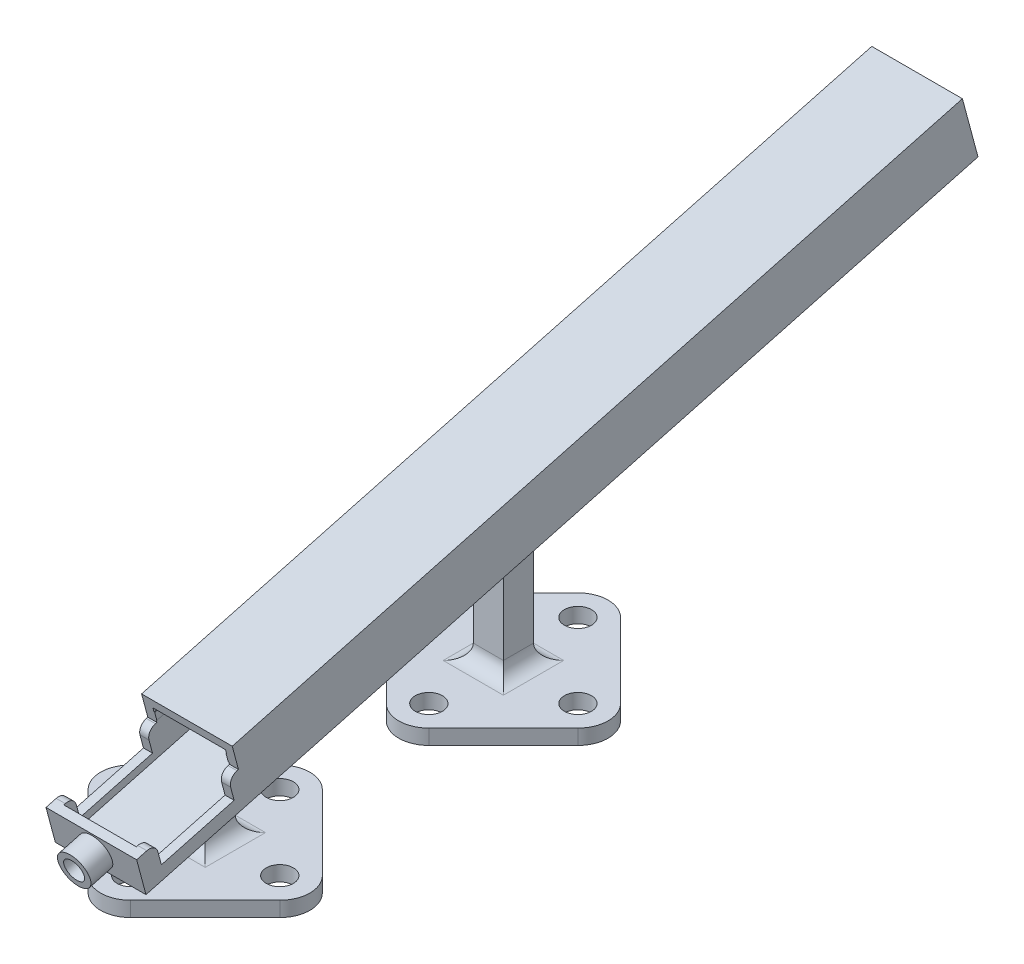
SolidWorks part; units mm, degrees
ref_plane "Front" through (0, 0, 0) normal (0, 0, 1) x (1, 0, 0)
ref_plane "Top" through (0, 0, 0) normal (0, 1, 0) x (1, 0, 0)
ref_plane "Right" through (0, 0, 0) normal (1, 0, 0) x (0, 0, -1)
ref_axis "Axis1" through (0, 55, 0) along (0, -1, 0)
ref_axis "Axis2" through (88.99, 0, 0) along (-1, 0, 0)
ref_axis "Axis3" through (0, 0, 55) along (0, 0, -1)
sketch "Sketch1" plane through (0, 0, 0) normal (0, 1, 0) x (1, 0, 0)
  line L0 (-24.75, 0) -> (0, 24.75) construction
  line L9 (-24.75, 0) -> (0, -24.75) construction
  line L11 (0, 24.75) -> (24.75, 0) construction
  line L12 (0, -24.75) -> (24.75, 0) construction
  line L13 (-24.75, 0) -> (24.75, 0) construction
  line L14 (0, 24.75) -> (0, -24.75) construction
  line L15 (-31.8211, 7.0711) -> (-7.0711, 31.8211)
  line L16 (7.0711, 31.8211) -> (31.8211, 7.0711)
  line L17 (7.0711, -31.8211) -> (31.8211, -7.0711)
  line L18 (-31.8211, -7.0711) -> (-7.0711, -31.8211)
  line L19 (0, -38.8921) -> (38.8921, 0) construction
  line L20 (-38.8921, 0) -> (0, -38.8921) construction
  line L21 (0, 38.8921) -> (38.8921, 0) construction
  line L22 (-38.8921, 0) -> (0, 38.8921) construction
  arc A4 (7.0711, -31.8211) -> (-7.0711, -31.8211) centre (0, -24.75) cw
  arc A5 (31.8211, 7.0711) -> (31.8211, -7.0711) centre (24.75, 0) cw
  arc A6 (-7.0711, 31.8211) -> (7.0711, 31.8211) centre (0, 24.75) cw
  arc A7 (-31.8211, 7.0711) -> (-31.8211, -7.0711) centre (-24.75, 0) ccw
  circle A8 centre (0, 24.75) radius 4.5
  circle A9 centre (24.75, 0) radius 4.5
  circle A10 centre (0, -24.75) radius 4.5
  circle A11 centre (-24.75, 0) radius 4.5
  point P1 (0, 0)
  dimension "D3" = 10
  dimension "D4" = 9
  dimension "D1" = 49.5
  dimension "D2" = 10
extrude "Boss-Extrude1" add sketch "Sketch1" along normal mid plane 5
ref_plane "Plane1" through (0, 0, 49.5) normal (0, 0, 1) x (1, 0, 0)
mirror "Mirror3" about plane through (0, 0, 49.5) normal (0, 0, 1) of bodies 101
sketch "Sketch2" plane through (0, 0, 0) normal (1, 0, 0) x (0, 0, -1)
  line L0 (-106.0711, 2.5) -> (-130.8211, 2.5) construction
  line L1 (-104, 2.5) -> (-94, 2.5)
  line L2 (-104, 2.5) -> (-104, 47.5)
  line L3 (-104, 47.5) -> (-94, 47.5)
  line L4 (-94, 2.5) -> (-94, 47.5)
  line L5 (-106.0711, -2.5) -> (-91.9289, -2.5) construction
  line L6 (-67.1789, -2.5) -> (-91.9289, -2.5) construction
  point P8 (-99, -2.5)
  point P9 (-99, 47.5)
  dimension "D1" = 10
  dimension "D2" = 50
extrude "Boss-Extrude2" add sketch "Sketch2" along normal mid plane 10 separate body
mirror "Mirror5" about plane through (0, 0, 49.5) normal (0, 0, 1) of bodies 103
sketch "Sketch3" plane through (0, 0, 0) normal (1, 0, 0) x (0, 0, -1)
  line L0 (-104, 17.5) -> (5, 46.7065)
  line L1 (-67.1789, -2.5) -> (-91.9289, -2.5) construction
  line L2 (-104, 47.5) -> (-104, 2.5) construction
  line L3 (-106.0711, 2.5) -> (-130.8211, 2.5) construction
  line L4 (5, 47.5) -> (5, 2.5) construction
  point P6 (-104, 17.5)
  dimension "D1" = 15
  dimension "D2" = 15
extrude "Cut-Extrude1" cut sketch "Sketch3" against normal through all both and the other way through all
sketch "Sketch4" plane through (0, 0, 0) normal (1, 0, 0) x (0, 0, -1)
  line L0 (-130.8211, 10.3133) -> (14.0678, 49.1362)
  line L1 (-130.8211, 10.3133) -> (-131.3387, 12.2452)
  line L2 (14.0678, 49.1362) -> (13.5502, 51.068)
  line L3 (-131.3387, 12.2452) -> (13.5502, 51.068)
  line L6 (-104, 17.5) -> (-94, 20.1795) construction
  dimension "D1" = 2
  dimension "D2" = 150
extrude "Boss-Extrude3" add sketch "Sketch4" along normal mid plane 24.1 separate body
combine bodies "Combine1" operation type add bodies to combine 102 106
combine bodies "Combine2" operation type add bodies to combine 107 101
fillet "Fillet1" radius 5 4 edges at (0, 2.5, 94) (-5, 2.5, 99) (0, 2.5, 104) (5, 2.5, 99)
fillet "Fillet2" radius 5 4 edges at (0, 2.5, 5) (0, 2.5, -5) (-5, 2.5, 0) (5, 2.5, 0)
sketch "Sketch5" plane through (0, 44.2596, 11.8593) normal (0, 0.9659, 0.2588) x (1, 0, 0)
  line L0 (12.05, -111.6442) -> (0, -111.6442) construction
  line L1 (12.05, 26.3058) -> (12.05, -123.6942) construction
  line L2 (0, -111.6442) -> (0, -123.6942) construction
  line L3 (12.05, -123.6942) -> (-12.05, -123.6942) construction
  line L4 (-11.83, -111.6442) -> (-12.05, -123.6942)
  line L5 (-12.05, -123.6942) -> (0, -123.6942)
  line L6 (0, -123.6942) -> (12.05, -123.6942)
  line L7 (12.05, -123.6942) -> (12.05, -111.6442)
  circle A0 centre (0, -111.6442) radius 8.73 construction
  circle A1 centre (0, -111.6442) radius 8.83
  circle A2 centre (0, -111.6442) radius 11.83
  dimension "D1" = 17.46
  dimension "D2" = 0.1
  dimension "D3" = 3
sketch "Sketch6" plane through (0, 44.2596, 11.8593) normal (0, 0.9659, 0.2588) x (1, 0, 0)
  line L4 (-12.05, 26.3058) -> (-12.05, -123.6942)
  line L5 (-12.05, -123.6942) -> (12.05, -123.6942)
  line L6 (12.05, -123.6942) -> (12.05, 26.3058)
  line L7 (12.05, 26.3058) -> (-12.05, 26.3058)
  line L8 (-12.05, 26.3058) -> (-12.05, -123.6942)
  line L9 (-12.05, -123.6942) -> (12.05, -123.6942)
  line L10 (12.05, -123.6942) -> (12.05, 26.3058)
  line L11 (12.05, 26.3058) -> (-12.05, 26.3058)
  line L16 (-15.05, 29.3058) -> (-15.05, -126.6942)
  line L17 (-15.05, -126.6942) -> (15.05, -126.6942)
  line L18 (15.05, -126.6942) -> (15.05, 29.3058)
  line L19 (15.05, 29.3058) -> (-15.05, 29.3058)
  line L20 (-15.05, 29.3058) -> (-15.05, -126.6942)
  line L21 (-15.05, -126.6942) -> (15.05, -126.6942)
  line L22 (15.05, -126.6942) -> (15.05, 29.3058)
  line L23 (15.05, 29.3058) -> (-15.05, 29.3058)
  dimension "D1" = 0
  dimension "D2" = 3
extrude "Boss-Extrude4" add sketch "Sketch6" against normal up to vertex (2 mm away) and the other way blind 10 up to point (12.05, 49.1362, -14.0678)
sketch "Sketch7" plane through (0, 53.9188, 14.4475) normal (0, 0.9659, 0.2588) x (1, 0, 0)
  line L0 (12.05, 26.3058) -> (12.05, -123.6942) construction
  line L1 (12.05, 26.3058) -> (12.05, -91.6942)
  line L3 (-12.05, 26.3058) -> (-12.05, -123.6942) construction
  line L4 (15.05, 29.3058) -> (-15.05, 29.3058)
  line L5 (-15.05, 29.3058) -> (-15.05, -126.6942)
  line L6 (-15.05, -126.6942) -> (15.05, -126.6942)
  line L7 (15.05, -126.6942) -> (15.05, 29.3058)
  line L8 (15.05, 29.3058) -> (-15.05, 29.3058)
  line L9 (-15.05, 29.3058) -> (-15.05, -91.6942)
  line L11 (15.05, -91.6942) -> (15.05, 29.3058)
  line L12 (12.05, 26.3058) -> (-12.05, 26.3058) construction
  line L14 (-12.05, 26.3058) -> (-12.05, -91.6942)
  line L15 (12.05, 26.3058) -> (-12.05, 26.3058)
  line L16 (15.05, -91.6942) -> (12.05, -91.6942)
  line L17 (-12.05, -91.6942) -> (-15.05, -91.6942)
  line L18 (-15.05, -126.6942) -> (15.05, -126.6942) construction
  dimension "D2" = 35
  dimension "D1" = 0
extrude "Boss-Extrude5" add sketch "Sketch7" along normal blind 5
sketch "Sketch8" plane through (0, 58.7485, 15.7416) normal (0, 0.9659, 0.2588) x (1, 0, 0)
  line L0 (-15.05, 29.3058) -> (-15.05, -91.6942) construction
  line L1 (-15.05, -91.6942) -> (15.05, -91.6942)
  line L2 (-15.05, -91.6942) -> (-15.05, 29.3058)
  line L3 (-15.05, 29.3058) -> (15.05, 29.3058)
  line L4 (15.05, -91.6942) -> (15.05, 29.3058)
extrude "Boss-Extrude6" add sketch "Sketch8" along normal blind 3
sketch "Sketch10" plane through (0, 6.8085, -25.4095) normal (0, -0.2588, 0.9659) x (1, 0, 0)
  line L4 (-12.05, 45.8209) -> (12.05, 45.8209)
  line L5 (12.05, 45.8209) -> (12.05, 60.8209)
  line L6 (12.05, 60.8209) -> (-12.05, 60.8209)
  line L7 (-12.05, 60.8209) -> (-12.05, 45.8209)
  line L8 (-12.05, 45.8209) -> (12.05, 45.8209)
  line L9 (12.05, 45.8209) -> (12.05, 60.8209)
  line L10 (12.05, 60.8209) -> (-12.05, 60.8209)
  line L11 (-12.05, 60.8209) -> (-12.05, 45.8209)
  dimension "D1" = 0
extrude "Cut-Extrude2" cut sketch "Sketch10" against normal up to next
sketch "Sketch11" plane through (0, 7.5849, -28.3073) normal (0, 0.2588, -0.9659) x (-1, 0, 0)
  line L0 (-12.05, 56.6209) -> (-11.85, 56.6209)
  line L1 (-12.05, 45.8209) -> (12.05, 45.8209) construction
  line L2 (-11.85, 56.6209) -> (-11.85, 59.3209)
  line L3 (-11.85, 59.3209) -> (-12.05, 59.3209)
  line L4 (-12.05, 60.8209) -> (-12.05, 45.8209) construction
  line L5 (-12.05, 59.3209) -> (-12.05, 56.6209)
  line L6 (0, 43.8209) -> (0, 45.8209) construction
  line L7 (-15.05, 43.8209) -> (15.05, 43.8209) construction
  line L8 (12.05, 59.3209) -> (12.05, 56.6209)
  line L9 (11.85, 59.3209) -> (12.05, 59.3209)
  line L10 (11.85, 56.6209) -> (11.85, 59.3209)
  line L11 (12.05, 56.6209) -> (11.85, 56.6209)
  dimension "D1" = 0.2
  dimension "D2" = 2.7
  dimension "D3" = 13.5
extrude "Boss-Extrude7" add sketch "Sketch11" against normal up to surface (121 mm away) up to face at (0, 33.3259, 103.8584)
sketch "Sketch12" plane through (0, 53.9188, 14.4475) normal (0, 0.9659, 0.2588) x (1, 0, 0)
  line L0 (-15.05, -91.6942) -> (-15.05, -126.6942) construction
  line L1 (-15.05, -95.1942) -> (-12.05, -95.1942)
  line L2 (-15.05, -95.1942) -> (-15.05, -120.1942)
  line L3 (-15.05, -120.1942) -> (-12.05, -120.1942)
  line L4 (-12.05, -95.1942) -> (-12.05, -120.1942)
  line L5 (-12.05, -91.6942) -> (-12.05, -123.6942) construction
  line L6 (-12.05, -123.6942) -> (-12.05, -120.1942) construction
  line L7 (-12.05, -95.1942) -> (-12.05, -91.6942) construction
  line L8 (-15.05, -91.6942) -> (15.05, -91.6942) construction
  line L9 (0, -91.6942) -> (0, -123.6942) construction
  line L10 (12.05, -123.6942) -> (-12.05, -123.6942) construction
  line L11 (12.05, -95.1942) -> (12.05, -91.6942) construction
  line L12 (12.05, -123.6942) -> (12.05, -120.1942) construction
  line L13 (12.05, -95.1942) -> (12.05, -120.1942)
  line L14 (15.05, -120.1942) -> (12.05, -120.1942)
  line L15 (15.05, -95.1942) -> (15.05, -120.1942)
  line L16 (15.05, -95.1942) -> (12.05, -95.1942)
  dimension "D1" = 25
extrude "Cut-Extrude3" cut sketch "Sketch12" against normal blind 7.5
sketch "Sketch13" plane through (0, -32.7909, 122.3772) normal (0, -0.2588, 0.9659) x (1, 0, 0)
  line L0 (-15.05, 55.8209) -> (15.05, 55.8209) construction
  line L1 (15.05, 55.8209) -> (15.05, 43.8209) construction
  circle A0 centre (0, 49.8209) radius 3.4
  circle A1 centre (0, 49.8209) radius 5.4
  point P4 (0, 55.8209)
  point P7 (15.05, 49.8209)
  dimension "D1" = 6.8
  dimension "D2" = 2
extrude "Boss-Extrude8" add sketch "Sketch13" along normal blind 7.5
sketch "Sketch14" plane through (0, -32.7909, 122.3772) normal (0, -0.2588, 0.9659) x (1, 0, 0)
  circle A0 centre (0, 49.8209) radius 3.4 construction
  circle A1 centre (0, 49.8209) radius 3.4
extrude "Cut-Extrude4" cut sketch "Sketch14" against normal up to next
fillet "Fillet3" radius 3 4 edges at (-13.55, 22.8103, 130.5462) (13.55, 22.8103, 130.5462) (13.55, 29.2808, 106.398) (-13.55, 29.2808, 106.398)
sketch "Sketch15" plane through (0, 7.5849, -28.3073) normal (0, 0.2588, -0.9659) x (-1, 0, 0)
  line L4 (-15.05, 63.8209) -> (-15.05, 43.8209)
  line L5 (-15.05, 43.8209) -> (15.05, 43.8209)
  line L6 (15.05, 43.8209) -> (15.05, 63.8209)
  line L7 (15.05, 63.8209) -> (-15.05, 63.8209)
  line L8 (-15.05, 63.8209) -> (-15.05, 43.8209)
  line L9 (-15.05, 43.8209) -> (15.05, 43.8209)
  line L10 (15.05, 43.8209) -> (15.05, 63.8209)
  line L11 (15.05, 63.8209) -> (-15.05, 63.8209)
  line L12 (12.05, 60.8209) -> (-12.05, 60.8209)
  line L13 (12.05, 59.3209) -> (12.05, 60.8209)
  line L14 (11.85, 59.3209) -> (12.05, 59.3209)
  line L15 (11.85, 56.6209) -> (11.85, 59.3209)
  line L16 (12.05, 56.6209) -> (11.85, 56.6209)
  line L17 (12.05, 45.8209) -> (12.05, 56.6209)
  line L18 (-12.05, 45.8209) -> (12.05, 45.8209)
  line L19 (-12.05, 56.6209) -> (-12.05, 45.8209)
  line L20 (-11.85, 56.6209) -> (-12.05, 56.6209)
  line L21 (-11.85, 59.3209) -> (-11.85, 56.6209)
  line L22 (-12.05, 59.3209) -> (-11.85, 59.3209)
  line L23 (-12.05, 60.8209) -> (-12.05, 59.3209)
  line L24 (12.05, 60.8209) -> (-12.05, 60.8209)
  line L25 (12.05, 59.3209) -> (12.05, 60.8209)
  line L26 (11.85, 59.3209) -> (12.05, 59.3209)
  line L27 (11.85, 56.6209) -> (11.85, 59.3209)
  line L28 (12.05, 56.6209) -> (11.85, 56.6209)
  line L29 (12.05, 45.8209) -> (12.05, 56.6209)
  line L30 (-12.05, 45.8209) -> (12.05, 45.8209)
  line L31 (-12.05, 56.6209) -> (-12.05, 45.8209)
  line L32 (-11.85, 56.6209) -> (-12.05, 56.6209)
  line L33 (-11.85, 59.3209) -> (-11.85, 56.6209)
  line L34 (-12.05, 59.3209) -> (-11.85, 59.3209)
  line L35 (-12.05, 60.8209) -> (-12.05, 59.3209)
  dimension "D1" = 0
  dimension "D2" = 0
extrude "Boss-Extrude9" add sketch "Sketch15" along normal blind 130
